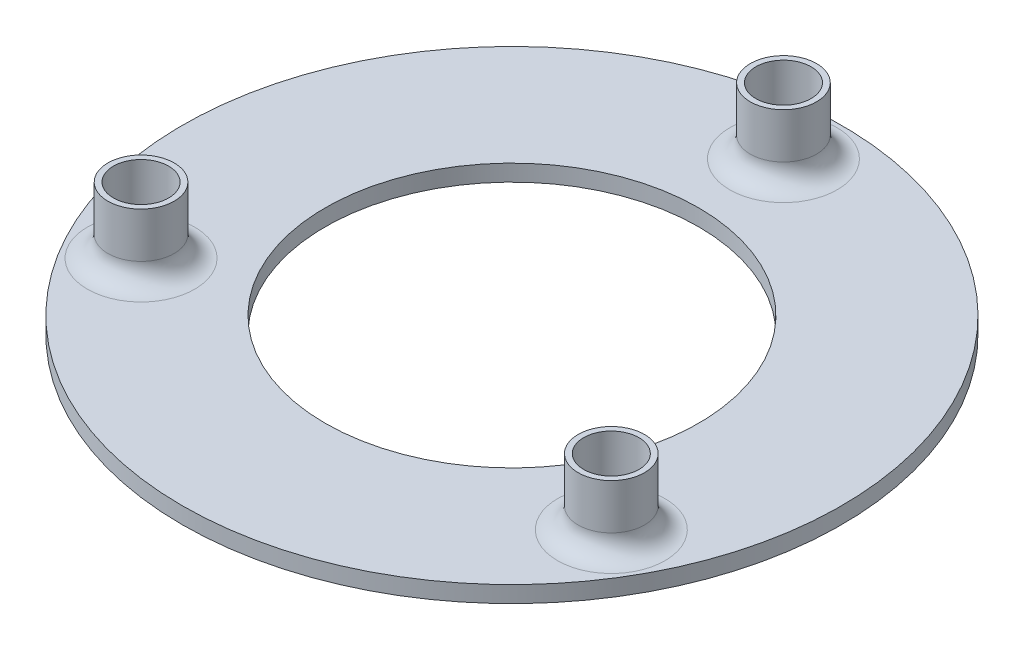
SolidWorks part; units mm, degrees
material "Custom Plastic PLA"
ref_plane "Front Plane" through (0, 0, 0) normal (0, 0, 1) x (1, 0, 0)
ref_plane "Top Plane" through (0, 0, 0) normal (0, 1, 0) x (1, 0, 0)
ref_plane "Right Plane" through (0, 0, 0) normal (1, 0, 0) x (0, 0, -1)
sketch "Sketch2" plane through (0, 0, 0) normal (0, 1, 0) x (1, 0, 0)
  line L0 (-48.3625, -58.5408) -> (-40.2504, -64.3884)
  line L1 (-48.3625, -58.5408) -> (-30.8198, -34.2046)
  line L2 (-40.2504, -64.3884) -> (-22.7077, -40.0521)
  line L3 (-30.8198, -34.2046) -> (-22.7077, -40.0521)
  line L4 (-64.3884, 40.2504) -> (-58.5408, 48.3625)
  line L5 (-64.3884, 40.2504) -> (-40.0521, 22.7077)
  line L6 (-58.5408, 48.3625) -> (-34.2046, 30.8198)
  line L7 (-40.0521, 22.7077) -> (-34.2046, 30.8198)
  line L8 (74.2187, 17.1051) -> (75.82, 7.2341)
  line L9 (74.2187, 17.1051) -> (44.6058, 12.3013)
  line L10 (75.82, 7.2341) -> (46.2071, 2.4303)
  line L11 (44.6058, 12.3013) -> (46.2071, 2.4303)
  line L12 (0, 0) -> (-26.7638, -37.1283) construction
  line L13 (0, 0) -> (-37.1283, 26.7638) construction
  line L14 (0, 0) -> (45.4064, 7.3658) construction
  line L15 (44.6967, 11.7411) -> (44.9142, 10.4002)
  line L16 (44.6967, 11.7411) -> (52.5935, 13.0221)
  line L17 (46.1112, 3.0211) -> (54.008, 4.3021)
  line L18 (52.5935, 13.0221) -> (52.811, 11.6812)
  line L19 (44.9142, 10.4002) -> (50.1885, 11.2558)
  line L20 (50.1885, 11.2558) -> (51.1534, 5.3076)
  line L21 (51.1534, 5.3076) -> (45.8791, 4.452)
  line L22 (50.4911, 11.3048) -> (52.811, 11.6812)
  line L23 (51.456, 5.3567) -> (53.7759, 5.733)
  line L24 (50.4911, 11.3048) -> (51.456, 5.3567)
  line L25 (45.8791, 4.452) -> (46.1112, 3.0211)
  line L26 (53.7759, 5.733) -> (54.008, 4.3021)
  line L27 (-41.032, 35.0293) -> (-41.8264, 33.9273)
  line L28 (-41.032, 35.0293) -> (-34.5423, 30.3513)
  line L29 (-46.1977, 27.8631) -> (-39.708, 23.1851)
  line L30 (-34.5423, 30.3513) -> (-35.3367, 29.2492)
  line L31 (-41.8264, 33.9273) -> (-38.8594, 31.7886)
  line L32 (-38.8594, 31.7886) -> (-42.3831, 26.9003)
  line L33 (-42.3831, 26.9003) -> (-45.3501, 29.039)
  line L34 (-38.6107, 31.6093) -> (-35.3367, 29.2492)
  line L35 (-42.1344, 26.721) -> (-38.8604, 24.361)
  line L36 (-38.6107, 31.6093) -> (-42.1344, 26.721)
  line L37 (-45.3501, 29.039) -> (-46.1977, 27.8631)
  line L38 (-38.8604, 24.361) -> (-39.708, 23.1851)
  line L39 (-23.2275, -39.6774) -> (-24.3295, -38.883)
  line L40 (-23.2275, -39.6774) -> (-27.9056, -46.1671)
  line L41 (-30.3937, -34.5117) -> (-35.0718, -41.0014)
  line L42 (-27.9056, -46.1671) -> (-29.0076, -45.3727)
  line L43 (-24.3295, -38.883) -> (-26.4683, -41.85)
  line L44 (-26.4683, -41.85) -> (-31.3566, -38.3263)
  line L45 (-31.3566, -38.3263) -> (-29.2178, -35.3593)
  line L46 (-26.6476, -42.0987) -> (-29.0076, -45.3727)
  line L47 (-31.5359, -38.575) -> (-33.8959, -41.849)
  line L48 (-26.6476, -42.0987) -> (-31.5359, -38.575)
  line L49 (-29.2178, -35.3593) -> (-30.3937, -34.5117)
  line L50 (-33.8959, -41.849) -> (-35.0718, -41.0014)
  circle A0 centre (0, 0) radius 65
  circle A1 centre (0.0009, 49.1455) radius 5
  circle A2 centre (0.0009, 49.1455) radius 6
  circle A3 centre (42.5633, -24.5747) radius 5
  circle A4 centre (42.5633, -24.5747) radius 6
  circle A5 centre (-42.5614, -24.5747) radius 5
  circle A6 centre (-42.5614, -24.5747) radius 6
  point P16 (0.0009, -0.0013)
  point P66 (0, 0)
  point P68 (0, 0)
  dimension "D1" = 10
  dimension "D2" = 30
  dimension "D3" = 8
  dimension "D4" = 46
sketch "Sketch4" plane through (0, 0, 0) normal (0, 1, 0) x (1, 0, 0)
  circle A1 centre (0.0013, 65.9046) radius 6.7051
  circle A2 centre (0.0013, 65.9046) radius 8.0461
  circle A3 centre (57.0778, -32.9549) radius 6.7051
  circle A4 centre (57.0778, -32.9549) radius 8.0461
  circle A5 centre (-57.0753, -32.9549) radius 6.7051
  circle A6 centre (-57.0753, -32.9549) radius 8.0461
  circle A7 centre (0, 0) radius 80
  circle A8 centre (0, 0) radius 45.3158
  dimension "D1" = 160
  dimension "D2" = 13.4101
  dimension "D3" = 65.9061
extrude "Boss-Extrude1" add sketch "Sketch4" along normal blind 4 contours A7 | A8
extrude "Boss-Extrude2" add sketch "Sketch4<3>" along normal blind 20 contours A6 A5 | A2 A1 | A4 A3 region at (-7.8172, 0, -65.9046) region at (49.2593, 0, 32.9549) region at (-64.8938, 0, 32.9549)
sketch "Sketch4<3>" plane through (0, 0, 0) normal (0, 1, 0) x (1, 0, 0) same geometry as "Sketch4"
fillet "Fillet1" radius 5 3 edges at (57.0778, 4, 41.0009) (0.0013, 4, -57.8585) (-57.0753, 4, 41.0009)
